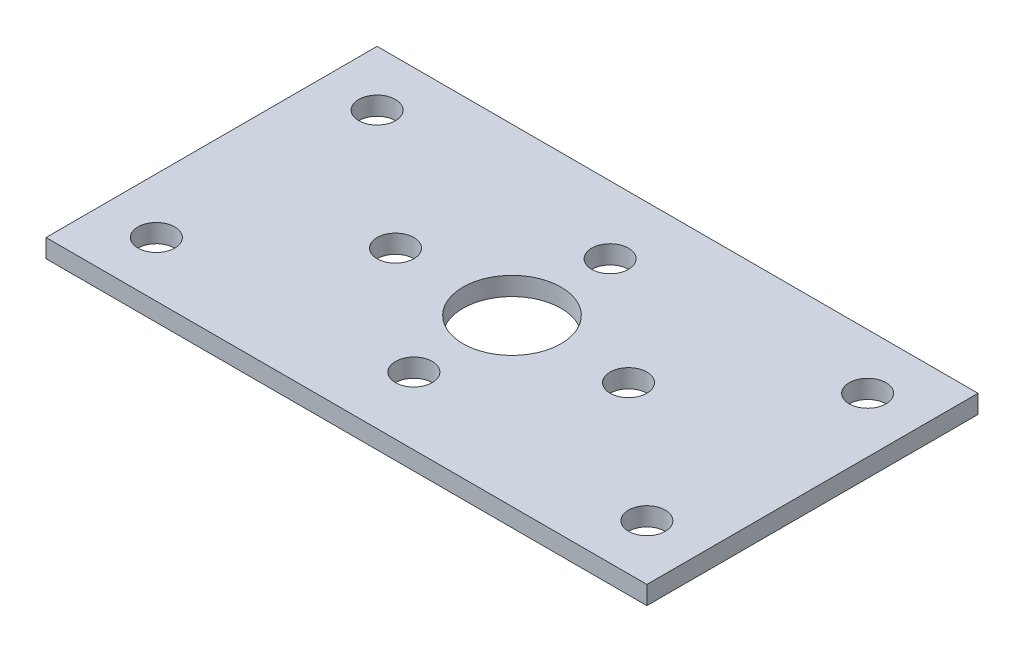
SolidWorks part; units mm, degrees
ref_plane "Front Plane" through (0, 0, 0) normal (0, 0, 1) x (1, 0, 0)
ref_plane "Top Plane" through (0, 0, 0) normal (0, 1, 0) x (1, 0, 0)
ref_plane "Right Plane" through (0, 0, 0) normal (1, 0, 0) x (0, 0, -1)
sketch "Sketch1" plane through (0, 0, 0) normal (0, 1, 0) x (1, 0, 0)
  line L1 (0, 0) -> (49, 0)
  line L2 (0, 0) -> (0, 27)
  line L3 (0, 27) -> (49, 27)
  line L4 (49, 0) -> (49, 27)
  dimension "D1" = 49
  dimension "D2" = 27
extrude "Boss-Extrude1" add sketch "Sketch1" along normal blind 1.5
sketch "Sketch2" plane through (0, 1.5, 0) normal (0, 1, 0) x (1, 0, 0)
  line L0 (0, 27) -> (0, 0) construction
  line L1 (49, 27) -> (0, 27) construction
  line L2 (0, 0) -> (49, 0) construction
  line L3 (49, 0) -> (49, 27) construction
  circle A0 centre (4.5, 22.5) radius 1.5
  circle A1 centre (4.5, 4.5) radius 1.5
  circle A2 centre (44.5, 4.5) radius 1.5
  circle A3 centre (44.5, 22.5) radius 1.5
  dimension "D1" = 4.5
  dimension "D3" = 4.5
  dimension "D2" = 4.5
  dimension "D4" = 4.5
  dimension "D5" = 18
  dimension "D6" = 4.5
  dimension "D7" = 4.5
  dimension "D8" = 4.5
  dimension "D9" = 4.5
extrude "Cut-Extrude1" cut sketch "Sketch2" against normal blind 10 and the other way blind 10
sketch "Sketch3" plane through (0, 1.5, 0) normal (0, 1, 0) x (1, 0, 0)
  line L0 (49, 27) -> (0, 27) construction
  line L1 (0, 27) -> (0, 0) construction
  line L2 (49, 0) -> (49, 27) construction
  circle A0 centre (15, 13.5) radius 1.5
  circle A1 centre (34, 13.5) radius 1.5
  circle A2 centre (24.5, 21.5) radius 1.5
  circle A3 centre (24.5, 5.5) radius 1.5
  circle A4 centre (24.5, 13.5) radius 4
  point P12 (49, 13.5)
  dimension "D1" = 13.5
  dimension "D3" = 19
  dimension "D11" = 24.5
  dimension "D2" = 15
  dimension "D4" = 16
  dimension "D5" = 5.5
  dimension "D6" = 8
  dimension "D7" = 9.5
  dimension "D8" = 9.5
  dimension "D9" = 15
  dimension "D10" = 5.5
  dimension "D12" = 13.5
  dimension "D13" = 24.5
extrude "Cut-Extrude2" cut sketch "Sketch3" against normal blind 10 and the other way blind 10
